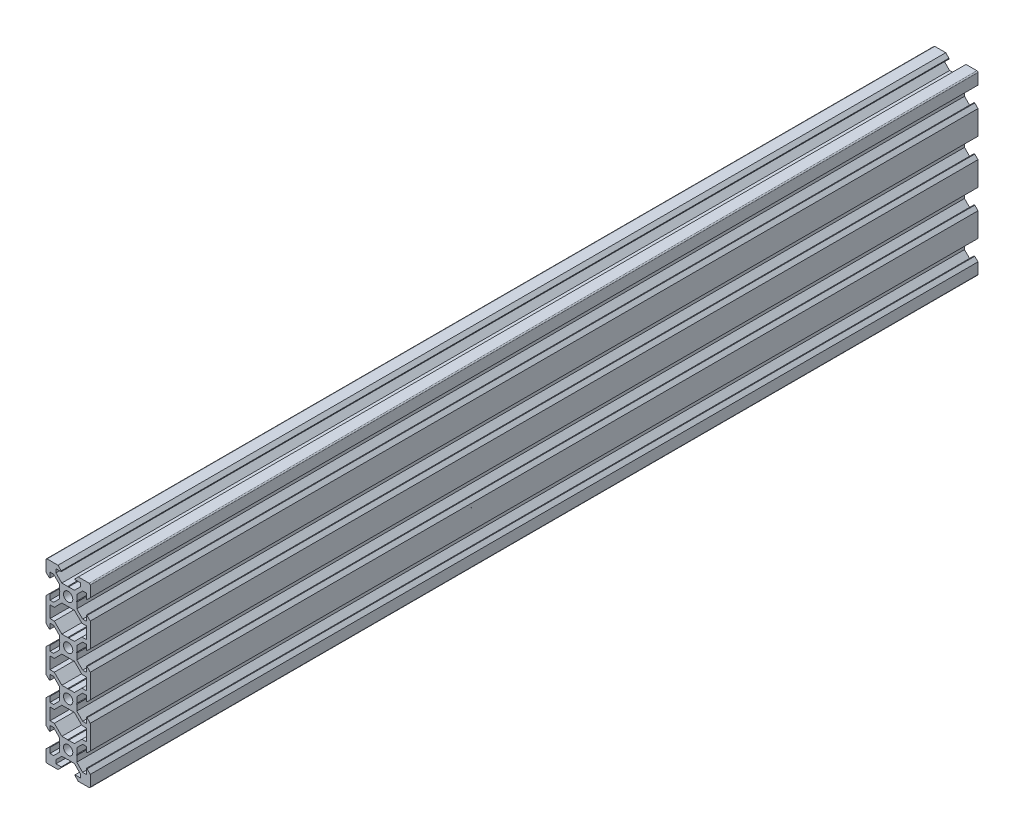
SolidWorks part; units mm, degrees
ref_plane "Plan de face" through (0, 0, 0) normal (0, 0, 1) x (1, 0, 0)
ref_plane "Plan de dessus" through (0, 0, 0) normal (0, 1, 0) x (1, 0, 0)
ref_plane "Plan de droite" through (0, 0, 0) normal (1, 0, 0) x (0, 0, -1)
ref_axis "Axe" through (0, 0, -13.782) along (0, 0, 1)
sketch "Esquisse1" plane through (0, 0, 0) normal (0, 0, 1) x (1, 0, 0)
  line L0 (0, 27.6392) -> (0, -27.6392) construction
  line L1 (-33.6074, 0) -> (33.6074, 0) construction
  line L2 (0, 0) -> (-22.2114, 22.2114) construction
  line L3 (-9.5, 10) -> (-4.58, 10)
  line L4 (-4.58, 10) -> (-3.125, 8.545)
  line L5 (-3.125, 8.545) -> (-3.125, 8.2)
  line L6 (-3.125, 8.2) -> (-5.5, 8.2)
  line L7 (-2.8393, 3.9) -> (-5.5, 6.5607)
  line L8 (-2.8393, 3.9) -> (-0.21, 3.9)
  line L9 (-5.5, 6.5607) -> (-5.5, 8.2)
  line L10 (0, 3.69) -> (0, 2.1)
  line L11 (-3.9, 2.8393) -> (-6.5607, 5.5)
  line L12 (-8.545, 3.125) -> (-8.2, 3.125)
  line L13 (-8.2, 3.125) -> (-8.2, 5.5)
  line L14 (-6.5607, 5.5) -> (-8.2, 5.5)
  line L15 (-10, 4.58) -> (-8.545, 3.125)
  line L16 (-10, 9.5) -> (-10, 4.58)
  line L17 (-0.21, 3.9) -> (0, 3.69)
  line L18 (-3.9, 2.8393) -> (-3.9, 0.21)
  line L19 (-6.2393, -12.7) -> (-8.2, -12.7)
  line L20 (-3.9, 0.21) -> (-3.69, 0)
  line L21 (-0.21, -3.9) -> (0, -3.69)
  line L22 (0, -3.69) -> (0, -2.1)
  line L23 (-6.5607, -5.5) -> (-8.2, -5.5)
  line L24 (-2.8393, -3.9) -> (-0.21, -3.9)
  line L25 (-8.545, -3.125) -> (-8.2, -3.125)
  line L26 (-10, -4.58) -> (-8.545, -3.125)
  line L27 (-8.2, -3.125) -> (-8.2, -5.5)
  line L28 (-2.8393, -3.9) -> (-6.2393, -7.3)
  line L29 (-3.9, -2.8393) -> (-6.5607, -5.5)
  line L30 (-3.9, -2.8393) -> (-3.9, -0.21)
  line L31 (-3.9, -0.21) -> (-3.69, 0)
  line L32 (-6.2393, -7.3) -> (-8.2, -7.3)
  line L33 (-8.2, -7.3) -> (-8.2, -12.7)
  line L34 (-8.2, -10) -> (-10, -10) construction
  line L35 (-10, -15.42) -> (-10, -4.58)
  line L36 (-3.9, -19.79) -> (-3.69, -20)
  line L37 (-3.9, -17.1607) -> (-3.9, -19.79)
  line L38 (-3.9, -17.1607) -> (-6.5607, -14.5)
  line L39 (-2.8393, -16.1) -> (-6.2393, -12.7)
  line L40 (-8.2, -16.875) -> (-8.2, -14.5)
  line L41 (-10, -15.42) -> (-8.545, -16.875)
  line L42 (-8.545, -16.875) -> (-8.2, -16.875)
  line L43 (-2.8393, -16.1) -> (-0.21, -16.1)
  line L44 (-6.5607, -14.5) -> (-8.2, -14.5)
  line L45 (0, -16.31) -> (0, -17.9)
  line L46 (-0.21, -16.1) -> (0, -16.31)
  line L47 (-8.2, -30) -> (-10, -30) construction
  line L48 (-3.69, -20) -> (0, -20) construction
  line L49 (-0.21, -23.9) -> (0, -23.69)
  line L50 (0, -23.69) -> (0, -22.1)
  line L51 (-6.5607, -25.5) -> (-8.2, -25.5)
  line L52 (-2.8393, -23.9) -> (-0.21, -23.9)
  line L53 (-8.545, -23.125) -> (-8.2, -23.125)
  line L54 (-10, -24.58) -> (-8.545, -23.125)
  line L55 (-8.2, -23.125) -> (-8.2, -25.5)
  line L56 (-2.8393, -23.9) -> (-6.2393, -27.3)
  line L57 (-3.9, -22.8393) -> (-6.5607, -25.5)
  line L58 (-3.9, -22.8393) -> (-3.9, -20.21)
  line L59 (-3.9, -20.21) -> (-3.69, -20)
  line L60 (-10, -24.58) -> (-10, -35.42)
  line L61 (-8.2, -32.7) -> (-8.2, -27.3)
  line L62 (-3.69, -40) -> (0, -40) construction
  line L63 (-8.2, -50) -> (-10, -50) construction
  line L64 (0, -60) -> (-22.2114, -82.2114) construction
  line L65 (-33.6074, -60) -> (33.6074, -60) construction
  line L66 (0, -87.6392) -> (0, -32.3608) construction
  line L67 (-6.2393, -32.7) -> (-8.2, -32.7)
  line L68 (-3.9, -39.79) -> (-3.69, -40)
  line L69 (-3.9, -37.1607) -> (-3.9, -39.79)
  line L70 (-3.9, -37.1607) -> (-6.5607, -34.5)
  line L71 (-2.8393, -36.1) -> (-6.2393, -32.7)
  line L72 (-8.2, -36.875) -> (-8.2, -34.5)
  line L73 (-10, -35.42) -> (-8.545, -36.875)
  line L74 (-8.545, -36.875) -> (-8.2, -36.875)
  line L75 (-6.2393, -27.3) -> (-8.2, -27.3)
  line L76 (-2.8393, -36.1) -> (-0.21, -36.1)
  line L77 (-6.5607, -34.5) -> (-8.2, -34.5)
  line L78 (0, -36.31) -> (0, -37.9)
  line L79 (-0.21, -36.1) -> (0, -36.31)
  line L80 (-0.21, -43.9) -> (0, -43.69)
  line L81 (0, -43.69) -> (0, -42.1)
  line L82 (-6.5607, -45.5) -> (-8.2, -45.5)
  line L83 (-2.8393, -43.9) -> (-0.21, -43.9)
  line L84 (-8.545, -43.125) -> (-8.2, -43.125)
  line L85 (-10, -44.58) -> (-8.545, -43.125)
  line L86 (-8.2, -43.125) -> (-8.2, -45.5)
  line L87 (-2.8393, -43.9) -> (-6.2393, -47.3)
  line L88 (-3.9, -42.8393) -> (-6.5607, -45.5)
  line L89 (-3.9, -42.8393) -> (-3.9, -40.21)
  line L90 (-3.9, -40.21) -> (-3.69, -40)
  line L91 (-10, -44.58) -> (-10, -55.42)
  line L92 (-8.2, -52.7) -> (-8.2, -47.3)
  line L93 (-6.2393, -52.7) -> (-8.2, -52.7)
  line L94 (-3.9, -59.79) -> (-3.69, -60)
  line L95 (-3.9, -57.1607) -> (-3.9, -59.79)
  line L96 (-3.9, -57.1607) -> (-6.5607, -54.5)
  line L97 (-2.8393, -56.1) -> (-6.2393, -52.7)
  line L98 (-8.2, -56.875) -> (-8.2, -54.5)
  line L99 (-10, -55.42) -> (-8.545, -56.875)
  line L100 (-8.545, -56.875) -> (-8.2, -56.875)
  line L101 (-2.8393, -56.1) -> (-0.21, -56.1)
  line L102 (-6.5607, -54.5) -> (-8.2, -54.5)
  line L103 (0, -56.31) -> (0, -57.9)
  line L104 (-0.21, -56.1) -> (0, -56.31)
  line L105 (-3.9, -60.21) -> (-3.69, -60)
  line L106 (-6.2393, -47.3) -> (-8.2, -47.3)
  line L107 (-3.9, -62.8393) -> (-3.9, -60.21)
  line L108 (-0.21, -63.9) -> (0, -63.69)
  line L109 (-10, -69.5) -> (-10, -64.58)
  line L110 (-10, -64.58) -> (-8.545, -63.125)
  line L111 (-6.5607, -65.5) -> (-8.2, -65.5)
  line L112 (-8.2, -63.125) -> (-8.2, -65.5)
  line L113 (-8.545, -63.125) -> (-8.2, -63.125)
  line L114 (-3.9, -62.8393) -> (-6.5607, -65.5)
  line L115 (0, -63.69) -> (0, -62.1)
  line L116 (-5.5, -66.5607) -> (-5.5, -68.2)
  line L117 (-2.8393, -63.9) -> (-0.21, -63.9)
  line L118 (-2.8393, -63.9) -> (-5.5, -66.5607)
  line L119 (-3.125, -68.2) -> (-5.5, -68.2)
  line L120 (-3.125, -68.545) -> (-3.125, -68.2)
  line L121 (-4.58, -70) -> (-3.125, -68.545)
  line L122 (-9.5, -70) -> (-4.58, -70)
  arc A0 (0, -2.1) -> (0, 2.1) centre (0, 0) cw
  arc A1 (-9.5, 10) -> (-10, 9.5) centre (-9.5, 9.5) ccw
  arc A2 (0, -42.1) -> (0, -37.9) centre (0, -40) cw
  arc A3 (-9.5, -70) -> (-10, -69.5) centre (-9.5, -69.5) cw
  arc A4 (0, -17.9) -> (0, -22.1) centre (0, -20) ccw
  arc A5 (0, -57.9) -> (0, -62.1) centre (0, -60) ccw
  point P4 (0, 0)
  point P7 (0, 0)
  point P30 (-10, 10)
  point P60 (0, -20)
  point P146 (-10, -70)
  dimension "D5" = 11
  dimension "D2" = 2.1
  dimension "D3" = 6.25
  dimension "D10" = 0.5
  dimension "D4" = 9.16
  dimension "D6" = 1.5
  dimension "D7" = 1.8
  dimension "D8" = 4.3
  dimension "D9" = 20
  dimension "D11" = 0.42
  dimension "D12" = 10
  dimension "D13" = 1.8
extrude "Boss.-Extru.1" add sketch "Esquisse1" along normal blind 401.2
sketch "Esquisse3" plane through (0, 0, 401.2) normal (0, 0, 1) x (1, 0, 0)
  line L0 (0, 0) -> (-9.8536, 9.8536) construction
  line L1 (-8.2, 8.2) -> (-8.2, 6.57)
  line L2 (-8.2, 6.57) -> (-7.54, 6.57)
  line L3 (-7.54, 6.57) -> (-6.57, 7.54)
  line L4 (-8.2, 3.125) -> (-8.2, 5.5) construction
  line L5 (-6.57, 8.2) -> (-6.57, 7.54)
  line L6 (-8.2, 8.2) -> (-6.57, 8.2)
  line L7 (-5.5, 6.5607) -> (-5.5, 8.2) construction
  line L8 (-10, -30) -> (6.918, -30) construction
  line L9 (-10, -24.58) -> (-10, -35.42) construction
  line L10 (-8.2, -68.2) -> (-6.57, -68.2)
  line L11 (-6.57, -68.2) -> (-6.57, -67.54)
  line L12 (-7.54, -66.57) -> (-6.57, -67.54)
  line L13 (-8.2, -66.57) -> (-7.54, -66.57)
  line L14 (-8.2, -68.2) -> (-8.2, -66.57)
  arc A0 (-9.5, 10) -> (-10, 9.5) centre (-9.5, 9.5) ccw construction
  point P13 (-7.055, 7.055)
  point P14 (-6.57, 7.87)
  point P26 (-7.055, -67.055)
  dimension "D1" = 1.07
extrude "Enlèv. mat.-Extru.1" [suppressed] cut sketch "Esquisse3" against normal through all
mirror "Symétrie1" about plane through (0, 3.69, 401.2) normal (-1, 0, 0) of "Enlèv. mat.-Extru.1", "Boss.-Extru.1"
